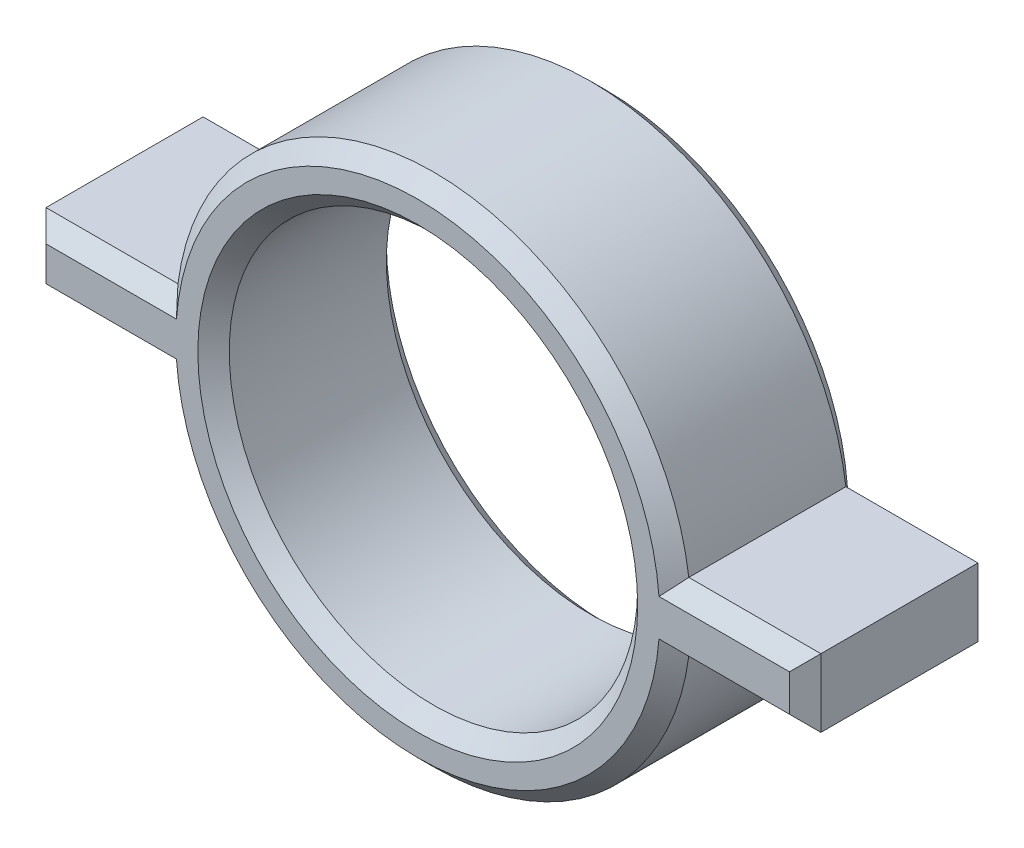
SolidWorks part; units mm, degrees
material "PLA"
ref_plane "Front Plane" through (0, 0, 0) normal (0, 0, 1) x (1, 0, 0)
ref_plane "Top Plane" through (0, 0, 0) normal (0, 1, 0) x (1, 0, 0)
ref_plane "Right Plane" through (0, 0, 0) normal (1, 0, 0) x (0, 0, -1)
sketch "Sketch1" plane through (0, 0, 0) normal (0, 0, 1) x (1, 0, 0)
  line L6 (8.1279, -1.0853) -> (12.3325, -1.0853)
  line L7 (12.3325, -1.0853) -> (12.3325, 1.0853)
  line L8 (12.3325, 1.0853) -> (8.1279, 1.0853)
  line L9 (-12.3325, 1.05) -> (-12.3325, -1.05)
  line L10 (-8.1325, 1.05) -> (-12.3325, 1.05)
  line L11 (-12.3325, -1.05) -> (-8.1325, -1.05)
  line L12 (0, 0) -> (16.0081, 0) construction
  line L13 (0, 0) -> (0, -4.3408) construction
  circle A1 centre (0, 0) radius 6.5 construction
  arc A4 (8.1279, 1.0853) -> (-8.1325, 1.05) centre (0, 0) ccw
  arc A5 (-8.1325, -1.05) -> (8.1279, -1.0853) centre (0, 0) ccw
  circle A6 centre (0, 0) radius 6.5
  dimension "D1" = 8.2
  dimension "D2" = 2.1
  dimension "D3" = 4.2
extrude "Boss-Extrude1" add sketch "Sketch1" along normal blind 6
chamfer "Chamfer1" distance 0.5 angle 45 18 edges at (6.5, 0, 0) (-12.3325, 0, 0) (-10.2325, -1.05, 0) (-0.0178, -8.2, 0) (10.2302, -1.0853, 0) (12.3325, 0, 0) (10.2302, 1.0853, 0) (-0.0178, 8.2, 0) (-10.2325, 1.05, 0) (6.5, 0, 6) (-0.0178, 8.2, 6) (10.2302, 1.0853, 6) (12.3325, 0, 6) (10.2302, -1.0853, 6) (-0.0178, -8.2, 6) (-10.2325, -1.05, 6) (-12.3325, 0, 6) (-10.2325, 1.05, 6)
